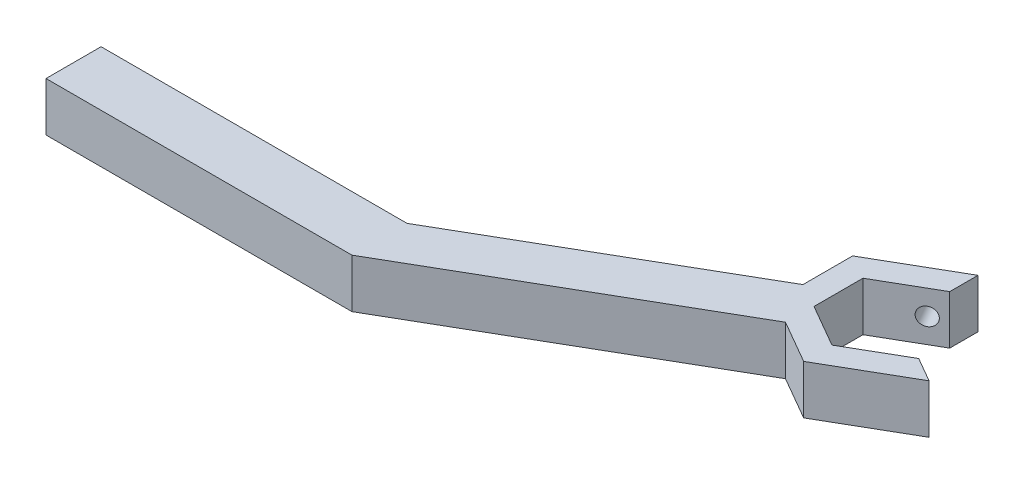
SolidWorks part; units mm, degrees
ref_plane "Front Plane" through (0, 0, 0) normal (0, 0, 1) x (1, 0, 0)
ref_plane "Top Plane" through (0, 0, 0) normal (0, 1, 0) x (1, 0, 0)
ref_plane "Right Plane" through (0, 0, 0) normal (1, 0, 0) x (0, 0, -1)
sketch "Sketch1" plane through (0, 0, 0) normal (0, 1, 0) x (1, 0, 0)
  line L0 (0, 0) -> (2.5, 0) construction
  line L1 (4.5, -4.5) -> (-4.5, -4.5)
  line L2 (4.5, -4.5) -> (4.5, 4.5) construction
  line L3 (4.5, 4.5) -> (-4.5, 4.5)
  line L4 (-4.5, -4.5) -> (-4.5, 4.5)
  line L5 (4.5, -4.5) -> (-4.5, 4.5) construction
  line L6 (4.5, 4.5) -> (-4.5, -4.5) construction
  line L7 (4.5, 4.5) -> (45.5, 4.5)
  line L8 (45.5, 4.5) -> (45.5, -4.5) construction
  line L9 (45.5, -4.5) -> (4.5, -4.5)
  line L10 (45.5, -4.5) -> (99.3971, 26.6175)
  line L11 (99.3971, 26.6175) -> (95.5, 33.3675)
  line L12 (95.5, 33.3675) -> (45.5, 4.5)
  line L13 (97.4486, 29.9925) -> (90.5204, 25.9925) construction
  line L14 (90.5204, 25.9925) -> (97.4486, 21.9925)
  line L15 (97.4486, 21.9925) -> (106.4389, 27.1831)
  line L18 (99.5107, 39.1831) -> (90.5204, 33.9925)
  line L19 (90.5204, 33.9925) -> (90.5204, 25.9925)
  line L21 (86.5204, 36.3019) -> (86.5204, 23.6831)
  line L22 (86.5204, 23.6831) -> (97.4486, 17.3737)
  line L23 (97.4486, 17.3737) -> (110.4389, 24.8737)
  line L26 (110.4389, 37.4925) -> (99.5107, 43.8019) construction
  line L27 (106.4389, 35.1831) -> (99.5107, 39.1831) construction
  line L28 (106.4389, 27.1831) -> (106.4389, 35.1831) construction
  line L29 (104.3768, 22.7814) -> (104.3768, 27.7814) [skipped]
  line L30 (105.4127, 33.3944) -> (101.0825, 35.8944) [skipped]
  line L31 (110.4389, 24.8737) -> (110.4389, 37.4925) construction
  line L32 (99.5107, 43.8019) -> (99.5107, 39.1831)
  line L33 (110.4389, 24.8737) -> (106.4389, 27.1831)
  line L34 (86.5204, 36.3019) -> (99.5107, 43.8019)
  line L35 (99.5107, 43.8019) -> (86.5204, 36.3019) construction
  circle A0 centre (0, 0) radius 2.5
  circle A1 centre (97.4486, 29.9925) radius 6.9282 construction
  dimension "D1" = 2
  dimension "D2" = 5
  dimension "D3" = 50
  dimension "D4" = 100
  dimension "D5" = 150
  dimension "D6" = 8
  dimension "D8" = 15
  dimension "D7" = 4
extrude "Boss-Extrude1" add sketch "Sketch1" along normal blind 4 contours L34 L21 L12 L19 L18 L32 | L21 L22 L10 L14 L19 L12 | L23 L33 L15 L14 L10 L22 | L22 L21 L12 L7 L3 L4 L1 L9 L10 A0 region at (0, 0, 3.4961) region at (89.4946, 0, -25.4003) region at (100.4282, 0, -22.1714) region at (92.1651, 0, -36.4835)
extrude "Boss-Extrude2" add sketch "Sketch1<3>" along normal blind 4 from surface contours L11 L12 L7 L3 L4 L1 L9 L10 A0 | A0 | L23 L33 L15 L14 L10 L22 | L21 L22 L10 L14 L19 L12 | L34 L21 L12 L19 L18 L32 region at (0, 0, 3.4961) region at (89.4946, 0, -25.4003) region at (100.4282, 0, -22.1714) region at (92.1651, 0, -36.4835) region at (0, 0, 0) starting at face at (75.8197, 4, -21.3541)
sketch "Sketch1<3>" plane through (0, 0, 0) normal (0, 1, 0) x (1, 0, 0) same geometry as "Sketch1"
sketch "Sketch4" plane through (5.9109, 0, 10.238) normal (-0.5, 0, -0.866) x (-0.866, 0, 0.5)
  line L0 (-93.0798, 4) -> (-103.0798, 4) construction
  line L4 (-108.0798, 0) -> (-93.0798, 0)
  line L5 (-93.0798, 0) -> (-93.0798, 8)
  line L6 (-93.0798, 8) -> (-108.0798, 8)
  line L7 (-108.0798, 8) -> (-108.0798, 0)
  line L8 (-108.0798, 0) -> (-93.0798, 0)
  line L9 (-93.0798, 0) -> (-93.0798, 8)
  line L10 (-93.0798, 8) -> (-108.0798, 8)
  line L11 (-108.0798, 8) -> (-108.0798, 0)
  circle A0 centre (-103.0798, 4) radius 1.45
  dimension "D2" = 2.9
  dimension "D3" = 10
  dimension "D1" = 0
extrude "Cut-Extrude1" cut sketch "Sketch4" against normal up to surface (4 mm away) contours A0 region at (95.1806, 4, -41.3019) up to face at (95.0155, 4, -36.5878)
